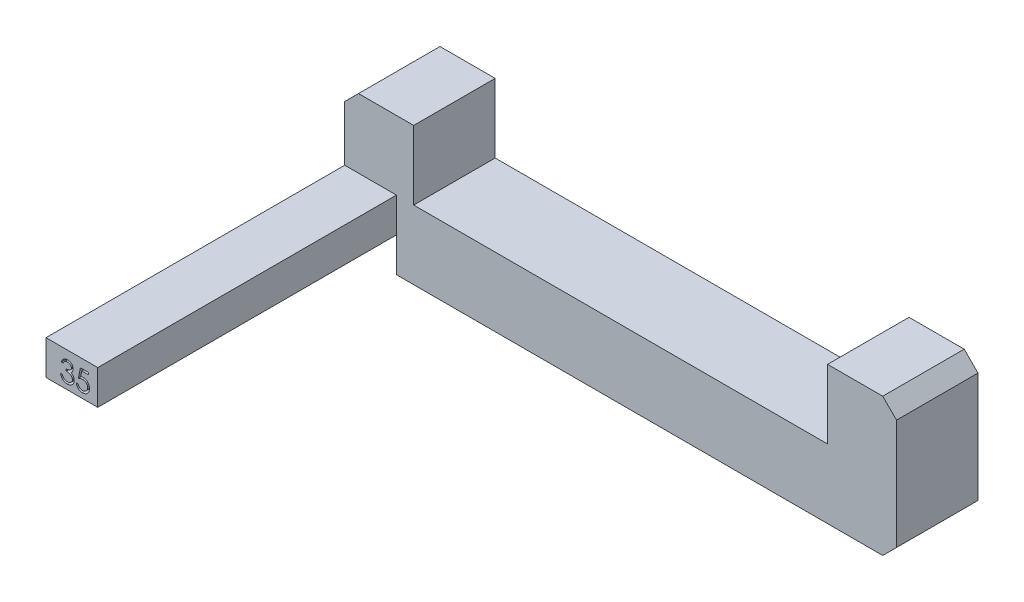
SolidWorks part; units mm, degrees
ref_plane "Front Plane" through (0, 0, 0) normal (0, 0, 1) x (1, 0, 0)
ref_plane "Top Plane" through (0, 0, 0) normal (0, 1, 0) x (1, 0, 0)
ref_plane "Right Plane" through (0, 0, 0) normal (1, 0, 0) x (0, 0, -1)
sketch "Sketch1" plane through (0, 0, 0) normal (0, 0, 1) x (1, 0, 0)
  line L1 (0, 0) -> (-101.6, 0)
  line L2 (0, 0) -> (0, 25.4)
  line L3 (0, 25.4) -> (-101.6, 25.4)
  line L4 (-101.6, 0) -> (-101.6, 25.4)
  line L5 (-12.7, 25.4) -> (-88.9, 25.4)
  line L6 (-12.7, 25.4) -> (-12.7, 12.7)
  line L7 (-12.7, 12.7) -> (-88.9, 12.7)
  line L8 (-88.9, 25.4) -> (-88.9, 12.7)
  point P9 (-50.8, 25.4)
  point P10 (-50.8, 12.7)
  dimension "D1" = 101.6
  dimension "D2" = 25.4
  dimension "D3" = 12.7
  dimension "D4" = 12.7
extrude "Boss-Extrude1" add sketch "Sketch1" along normal blind 15 contours L8 L3 L4 L1 L2 L6 L7 region at (-50.8, 8.89, 0)
sketch "Sketch2" plane through (0, 0, 15) normal (0, 0, 1) x (1, 0, 0)
  line L0 (-101.6, 0) -> (-101.6, 25.4) construction
  line L1 (-101.6, 6.35) -> (-92.075, 6.35)
  line L2 (-101.6, 6.35) -> (-101.6, 12.7)
  line L3 (-101.6, 12.7) -> (-92.075, 12.7)
  line L4 (-92.075, 6.35) -> (-92.075, 12.7)
  line L5 (0, 0) -> (-101.6, 0) construction
  dimension "D1" = 9.525
  dimension "D2" = 6.35
  dimension "D3" = 6.35
extrude "Boss-Extrude2" add sketch "Sketch2" along normal blind 55
sketch "Sketch3" plane through (0, 0, 70) normal (0, 0, 1) x (1, 0, 0)
  line L0 (-101.6, 12.7) -> (-101.6, 6.35) construction
  line L1 (-101.6, 6.35) -> (-92.075, 6.35) construction
  text T0 "35" font "Century Gothic" height in points 14
  dimension "D1" = 2.54
  dimension "D2" = 1.016
extrude "Cut-Extrude1" cut sketch "Sketch3" against normal blind 2
chamfer "Chamfer1" distance 2.54 angle 45 4 edges at (0, 0, 7.5) (-101.6, 0, 7.5) (0, 25.4, 7.5) (-101.6, 25.4, 7.5)
sketch "Sketch4" plane through (0, 0, 15) normal (0, 0, 1) x (1, 0, 0)
  line L0 (-101.6, 2.54) -> (-101.6, 6.35) construction
  line L1 (-92.075, 6.35) -> (-101.6, 6.35)
  line L2 (-92.075, 6.35) -> (-92.075, 0)
  line L3 (-92.075, 0) -> (-101.6, 0)
  line L4 (-101.6, 6.35) -> (-101.6, 0)
  line L5 (-2.54, 0) -> (-99.06, 0) construction
extrude "Cut-Extrude2" cut sketch "Sketch4" against normal through all
